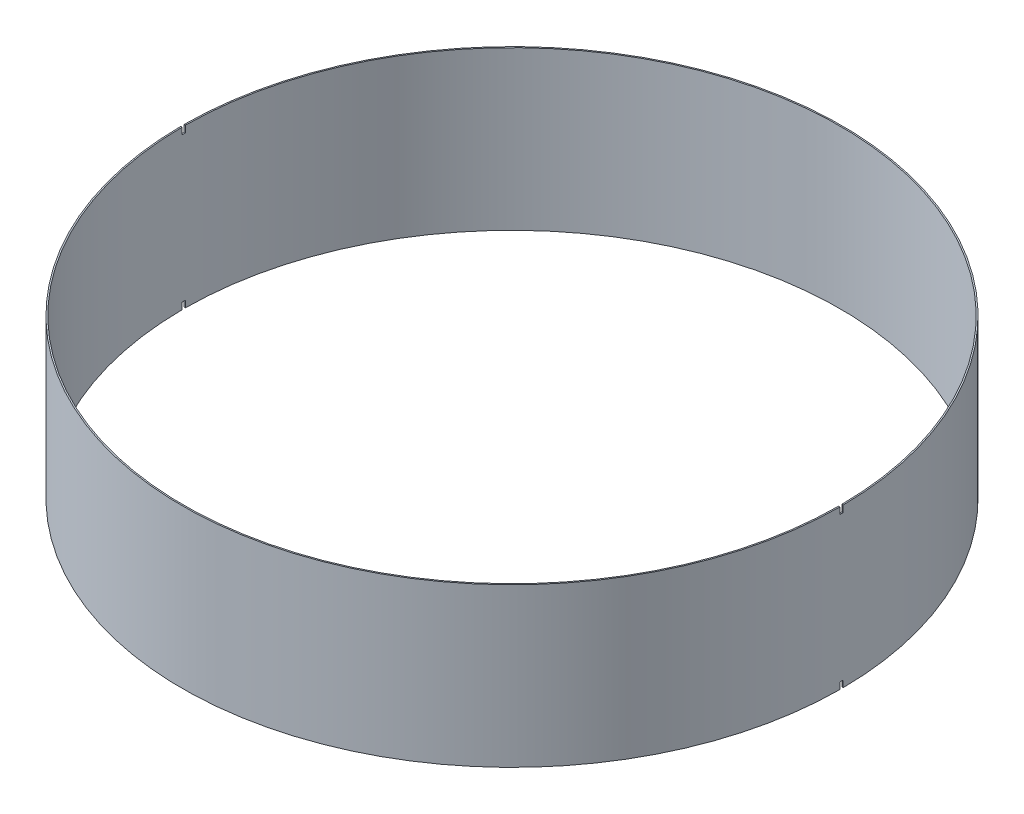
SolidWorks part; units mm, degrees
ref_plane "Front Plane" through (0, 0, 0) normal (0, 0, 1) x (1, 0, 0)
ref_plane "Top Plane" through (0, 0, 0) normal (0, 1, 0) x (1, 0, 0)
ref_plane "Right Plane" through (0, 0, 0) normal (1, 0, 0) x (0, 0, -1)
sketch "Эскиз1" plane through (0, 0, 0) normal (0, 1, 0) x (1, 0, 0)
  circle A0 centre (0, 0) radius 50
  circle A1 centre (0, 0) radius 49.8
extrude "Бобышка-Вытянуть1" add sketch "Эскиз1" along normal blind 24
sketch "Эскиз3" plane through (0, 0, 0) normal (1, 0, 0) x (0, 0, -1)
  line L0 (0, 24) -> (0.25, 24)
  line L8 (0, 24) -> (-0.25, 24)
  line L9 (-0.25, 24) -> (-0.25, 23)
  line L10 (-0.25, 23) -> (0.25, 23)
  line L11 (0.25, 23) -> (0.25, 24)
  line L12 (0, 0) -> (0, 24) construction
  line L14 (0, 12) -> (3.0275, 12) construction
  line L15 (0.25, 1) -> (0.25, 0)
  line L16 (-0.25, 1) -> (0.25, 1)
  line L17 (-0.25, 0) -> (-0.25, 1)
  line L18 (0, 0) -> (-0.25, 0)
  line L19 (0, 0) -> (0.25, 0)
extrude "Вырез-Вытянуть2" cut sketch "Эскиз3" against normal blind 52 and the other way blind 52
